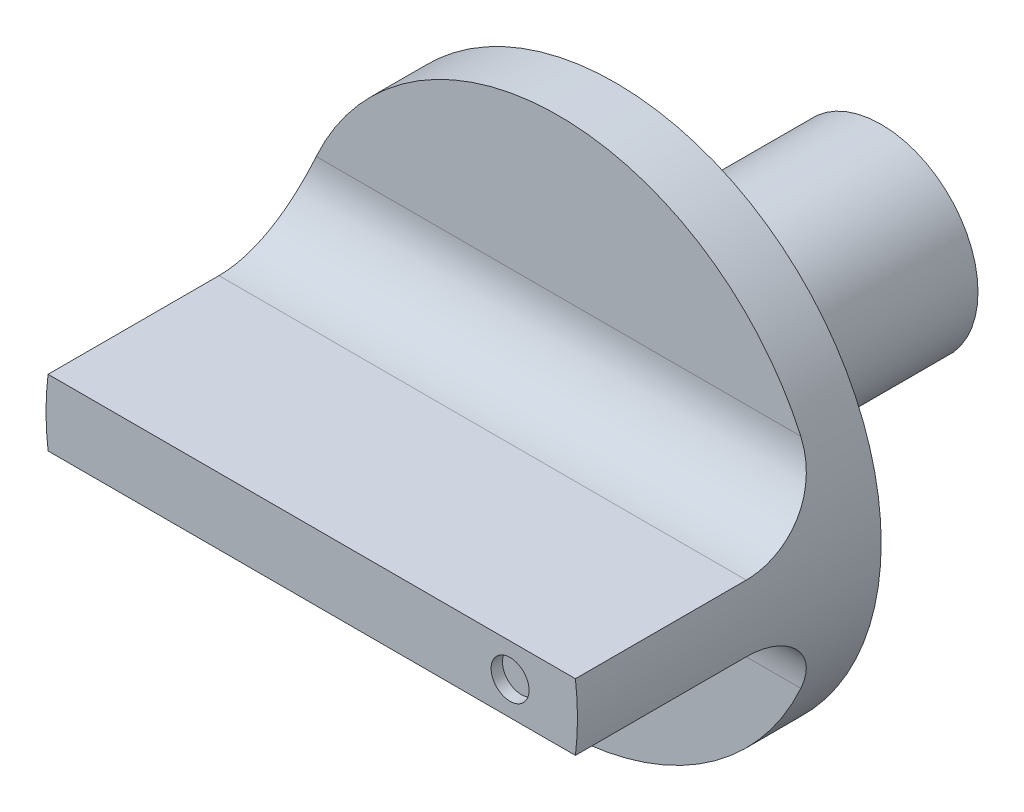
SolidWorks part; units mm, degrees
material "ABS"
ref_plane "Alzado" through (0, 0, 0) normal (0, 0, 1) x (1, 0, 0)
ref_plane "Planta" through (0, 0, 0) normal (0, 1, 0) x (1, 0, 0)
ref_plane "Vista lateral" through (0, 0, 0) normal (1, 0, 0) x (0, 0, -1)
sketch "Croquis1" plane through (0, 0, 0) normal (0, 0, 1) x (1, 0, 0)
  circle A0 centre (0, 0) radius 14
  dimension "D1" = 28
extrude "Saliente-Extruir1" add sketch "Croquis1" along normal blind 3
sketch "Croquis2" plane through (0, 0, 3) normal (0, 0, 1) x (1, 0, 0)
  line L0 (-15.7794, 0) -> (17.2649, 0) construction
  line L1 (-13.8902, -1.75) -> (13.8902, -1.75)
  line L3 (-13.8902, 1.75) -> (13.8902, 1.75)
  circle A1 centre (0, 0) radius 14 construction
  arc A2 (-13.8902, 1.75) -> (-13.8902, -1.75) centre (0, 0) ccw
  arc A3 (13.8902, -1.75) -> (13.8902, 1.75) centre (0, 0) ccw
  point P0 (0, 0)
  dimension "D1" = 3.5
extrude "Saliente-Extruir2" add sketch "Croquis2" along normal blind 13
sketch "Croquis3" plane through (0, 0, 0) normal (0, 0, -1) x (-1, 0, 0)
  line L0 (0, 6.283) -> (0, -5.1) construction
  line L1 (-1.1, 2.8983) -> (-1.1, -2.8983)
  line L2 (-1.1, 6.283) -> (-1.1, -6.6975) construction
  line L4 (0, 6.283) -> (0, -6.6975) construction
  arc A0 (-1.1, -2.8983) -> (-1.1, 2.8983) centre (0, 0) ccw
  circle A1 centre (0, 0) radius 5.1
  circle A2 centre (0, 0) radius 3.1 construction
  dimension "D1" = 6.2
  dimension "D2" = 2
  dimension "D3" = 1.1
extrude "Saliente-Extruir3" add sketch "Croquis3" along normal blind 14
fillet "Redondeo1" radius 4 2 edges
fillet "Redondeo2" radius 3 1 edges at (5.1, 0, 0)
sketch "Croquis4" plane through (0, 0, 16) normal (0, 0, 1) x (1, 0, 0)
  circle A0 centre (10.4487, 0) radius 1
  dimension "D1" = 2
extrude "Cortar-Extruir1" cut sketch "Croquis4" against normal blind 0.6
